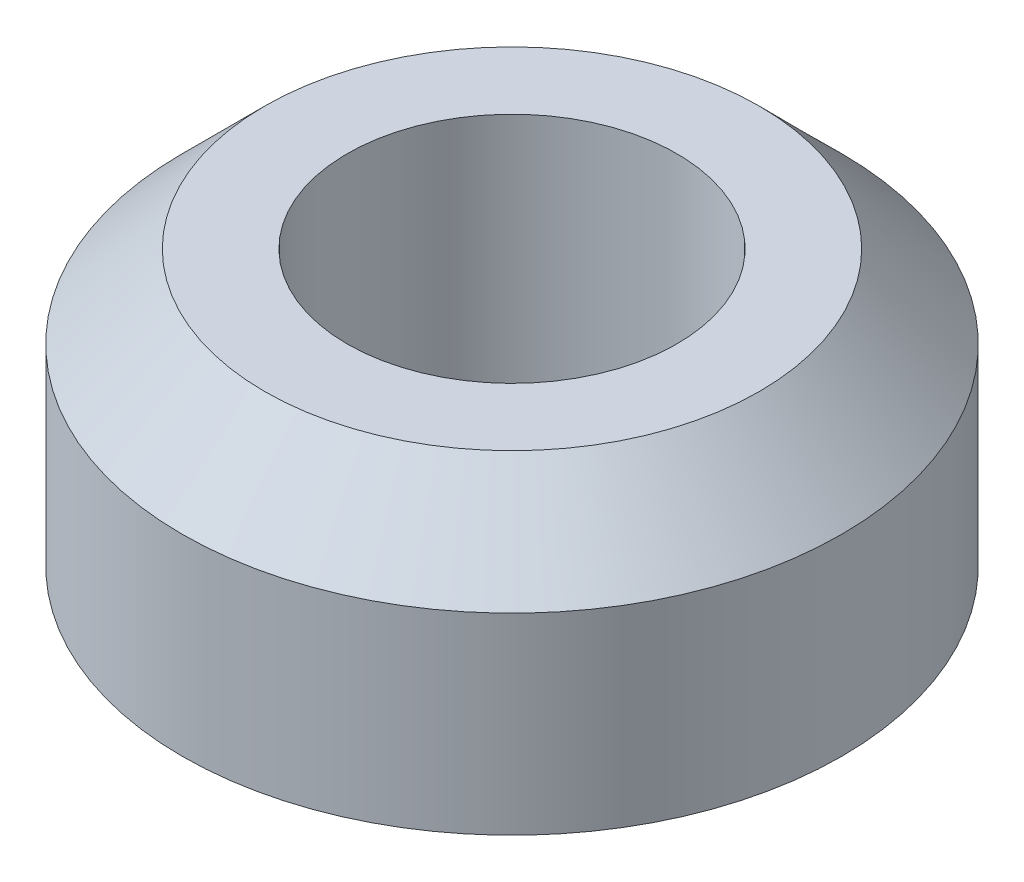
SolidWorks part; units mm, degrees
ref_plane "Front Plane" through (0, 0, 0) normal (0, 0, 1) x (1, 0, 0)
ref_plane "Top Plane" through (0, 0, 0) normal (0, 1, 0) x (1, 0, 0)
ref_plane "Right Plane" through (0, 0, 0) normal (1, 0, 0) x (0, 0, -1)
sketch "Sketch1" plane through (0, 0, 0) normal (0, 1, 0) x (1, 0, 0)
  circle A0 centre (0, 0) radius 3
  circle A1 centre (0, 0) radius 6
  dimension "D1" = 6
  dimension "12" = 12
extrude "Boss-Extrude1" add sketch "Sketch1" along normal blind 5
chamfer "Chamfer1" distance 1.5 angle 45 1 edges at (0, 5, 6)
